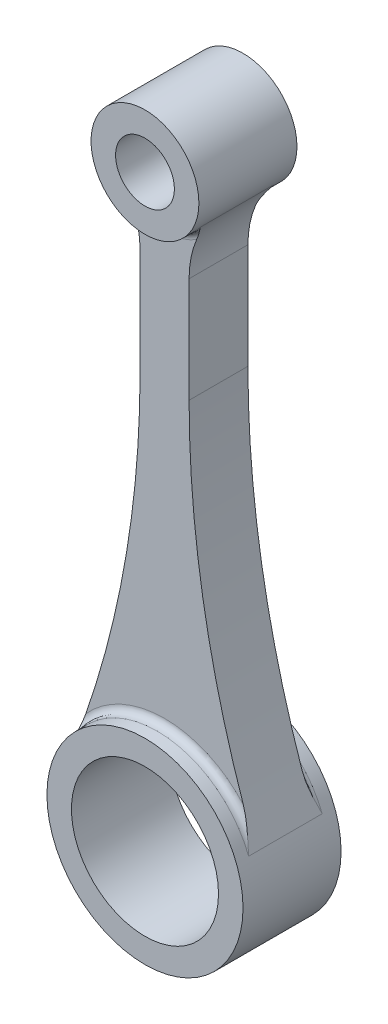
SolidWorks part; units mm, degrees
ref_plane "Płaszczyzna przednia" through (0, 0, 0) normal (0, 0, 1) x (1, 0, 0)
ref_plane "Płaszczyzna górna" through (0, 0, 0) normal (0, 1, 0) x (1, 0, 0)
ref_plane "Płaszczyzna prawa" through (0, 0, 0) normal (1, 0, 0) x (0, 0, -1)
sketch "Szkic1" plane through (0, 0, 0) normal (0, 0, 1) x (1, 0, 0)
  circle A0 centre (0, 0) radius 15
  circle A1 centre (0, 0) radius 20
  circle A2 centre (0, 120) radius 6
  circle A3 centre (0, 120) radius 11
  dimension "D1" = 12
  dimension "D2" = 22
  dimension "D3" = 30
  dimension "D4" = 40
  dimension "D5" = 120
extrude "Dodanie-wyciągnięcie1" add sketch "Szkic1" along normal mid plane 20
sketch "Szkic2" plane through (0, 0, 0) normal (0, 0, 1) x (1, 0, 0)
  line L0 (0, 120) -> (0, 0) construction
  line L1 (5, 110.202) -> (5, 80.202)
  line L2 (-5, 110.202) -> (-5, 80.202)
  circle A0 centre (0, 120) radius 11 construction
  arc A1 (-5, 110.202) -> (5, 110.202) centre (0, 120) ccw
  circle A2 centre (0, 0) radius 20 construction
  arc A3 (18.6481, 7.2283) -> (-18.6481, 7.2283) centre (0, 0) ccw
  arc A4 (5, 80.202) -> (18.6481, 7.2283) centre (206.9122, 80.202) ccw
  arc A5 (-5, 80.202) -> (-18.6481, 7.2283) centre (-206.9122, 80.202) cw
  dimension "D1" = 30
  dimension "D2" = 5
extrude "Dodanie-wyciągnięcie2" add sketch "Szkic2" along normal mid plane 12
fillet "Zaokrąglenie3" radius 1.5 2 edges at (0, 109, 6) (0, 109, -6)
fillet "Zaokrąglenie4" radius 20 2 edges at (-5, 110.202, 0) (5, 110.202, 0)
fillet "Zaokrąglenie5" radius 1.5 2 edges at (0, 20, -6) (0, 20, 6)
